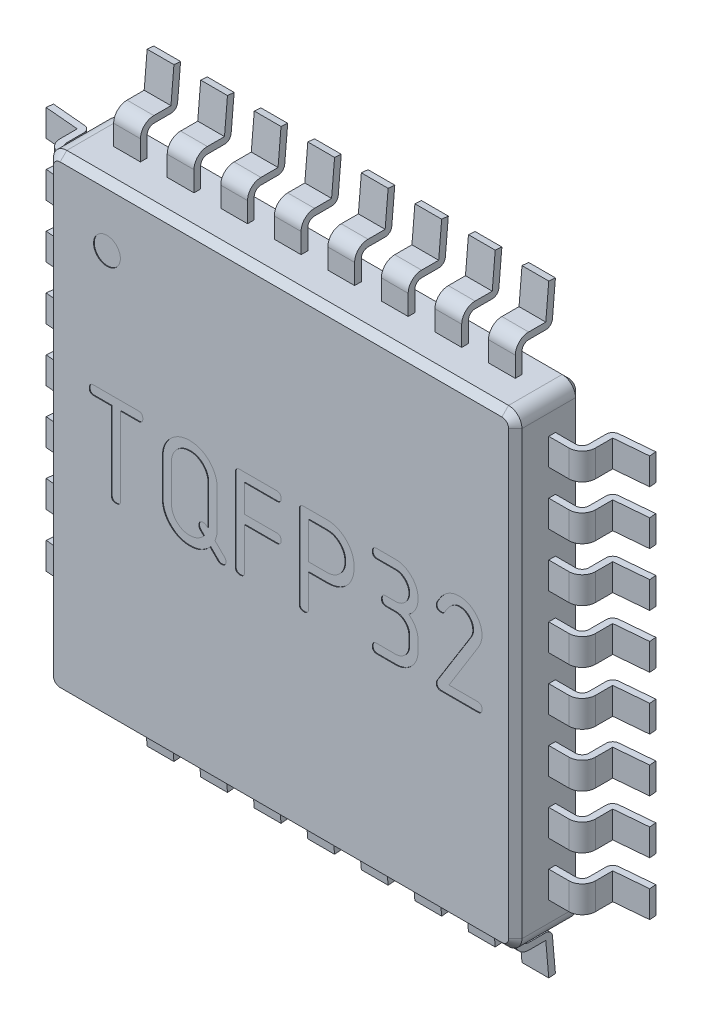
SolidWorks part; units mm, degrees
ref_plane "Спереди" through (0, 0, 0) normal (0, 0, 1) x (1, 0, 0)
ref_plane "Сверху" through (0, 0, 0) normal (0, 1, 0) x (1, 0, 0)
ref_plane "Справа" through (0, 0, 0) normal (1, 0, 0) x (0, 0, -1)
ref_axis "Ось1" through (0, 0, -0.055) along (0, 0, 1)
sketch "Эскиз1" plane through (0, 0, 0) normal (0, 0, 1) x (1, 0, 0)
  line L0 (0, 0) -> (-4.5, 0) construction
  line L1 (-3.5, -3.5) -> (3.5, -3.5)
  line L2 (-3.5, -3.5) -> (-3.5, 3.5)
  line L3 (-3.5, 3.5) -> (3.5, 3.5)
  line L4 (3.5, -3.5) -> (3.5, 3.5)
  line L5 (-3.5, -3.5) -> (3.5, 3.5) construction
  line L6 (-3.5, 3.5) -> (3.5, -3.5) construction
  line L7 (-4.5, -4.5) -> (4.5, -4.5)
  line L8 (-4.5, -4.5) -> (-4.5, 4.5)
  line L9 (-4.5, 4.5) -> (4.5, 4.5)
  line L10 (4.5, -4.5) -> (4.5, 4.5)
  line L11 (-4.5, -4.5) -> (4.5, 4.5) construction
  line L12 (-4.5, 4.5) -> (4.5, -4.5) construction
  point P0 (0, 0)
  point P6 (0, 0)
  point P13 (-3.5, 0.4)
  point P14 (-3.5, 1.2)
  point P15 (-3.5, 2)
  point P16 (-3.5, 2.8)
  point P17 (-3.5, -2.8)
  point P18 (-3.5, -2)
  point P19 (-3.5, -1.2)
  point P20 (-3.5, -0.4)
  dimension "D1" = 7
  dimension "D2" = 7
  dimension "D3" = 9
  dimension "D4" = 9
  dimension "D5" = 0.8
  dimension "D6" = 0.8
  dimension "D7" = 0.8
  dimension "D8" = 0.8
ref_plane "Плоскость1" through (0, 0, 0.1) normal (0, 0, 1) x (1, 0, 0)
ref_plane "Плоскость2" through (0, 2.8, 0) normal (0, 1, 0) x (-1, 0, 0)
sketch "Эскиз2" plane through (0, 0, 0.1) normal (0, 0, 1) x (1, 0, 0)
  line L0 (-3.5, 3.5) -> (3.5, 3.5) construction
  line L1 (-3.5, -3.5) -> (-3.5, 3.5) construction
  line L2 (-3.5, -3.5) -> (3.5, -3.5) construction
  line L3 (3.5, -3.5) -> (3.5, 3.5) construction
  line L4 (-3.3, 3.5) -> (3.3, 3.5)
  line L5 (-3.5, -3.3) -> (-3.5, 3.3)
  line L6 (-3.3, -3.5) -> (3.3, -3.5)
  line L7 (3.5, -3.3) -> (3.5, 3.3)
  arc A0 (-3.5, -3.3) -> (-3.3, -3.5) centre (-3.3, -3.3) ccw
  arc A1 (3.3, -3.5) -> (3.5, -3.3) centre (3.3, -3.3) ccw
  arc A2 (3.3, 3.5) -> (3.5, 3.3) centre (3.3, 3.3) cw
  arc A3 (-3.3, 3.5) -> (-3.5, 3.3) centre (-3.3, 3.3) ccw
  dimension "D1" = 0.2
extrude "Бобышка-Вытянуть1" add sketch "Эскиз2" along normal blind 1
chamfer "Фаска1" distance 0.1 angle 45 16 edges at (0, 3.5, 0.1) (-3.4414, 3.4414, 0.1) (3.4414, 3.4414, 0.1) (-3.5, 0, 0.1) (3.5, 0, 0.1) (-3.4414, -3.4414, 0.1) (3.4414, -3.4414, 0.1) (0, -3.5, 0.1) (0, 3.5, 1.1) (-3.4414, 3.4414, 1.1) (3.4414, 3.4414, 1.1) (-3.5, 0, 1.1) (3.5, 0, 1.1) (-3.4414, -3.4414, 1.1) (3.4414, -3.4414, 1.1) (0, -3.5, 1.1)
sketch "Эскиз3" plane through (0, 2.8, 0) normal (0, 1, 0) x (-1, 0, 0)
  line L0 (3.5, 0.5) -> (3.8, 0.5)
  line L1 (3.9, 0.4) -> (3.9, 0.1441)
  line L2 (3.9913, 0.0445) -> (4.5, 0)
  line L3 (4.95, 0) -> (-4.95, 0) construction
  line L4 (3.5, 0.6) -> (3.8, 0.6)
  line L5 (4, 0.4) -> (4, 0.1441)
  line L6 (4, 0.1441) -> (4.5087, 0.0996)
  line L7 (3.5, 0.5) -> (3.5, 0.6)
  line L8 (4.5, 0) -> (4.5087, 0.0996)
  arc A0 (3.9, 0.1441) -> (3.9913, 0.0445) centre (4, 0.1441) ccw
  arc A1 (3.8, 0.5) -> (3.9, 0.4) centre (3.8, 0.4) cw
  arc A2 (3.8, 0.6) -> (4, 0.4) centre (3.8, 0.4) cw
  arc A3 (4, 0.1441) -> (4, 0.1441) centre (4, 0.1441) ccw
  dimension "D1" = 0.1
  dimension "D2" = 0.6
  dimension "D3" = 5
  dimension "D4" = 0.5
  dimension "D5" = 0.1
extrude "Бобышка-Вытянуть2" add sketch "Эскиз3" along normal blind 0.2 and the other way blind 0.2
pattern_linear "Линейный массив1" count 8 spacing 0.8 along (0, -1, 0) of "Бобышка-Вытянуть2"
pattern_circular "Круговой массив1" count 4 over 360 about axis through (0, 0, -0.055) along (0, 0, 1) of "Бобышка-Вытянуть2", "Линейный массив1"
sketch "Эскиз4" plane through (0, 0, 1.1) normal (0, 0, 1) x (1, 0, 0)
  circle A0 centre (-2.6, 2.6) radius 0.2
  text T0 "TQFP32" font "ГОСТ тип А" height in points 6
  dimension "D1" = 0.4
  dimension "D2" = 3
  dimension "D3" = 0.6
extrude "Вырез-Вытянуть1" cut sketch "Эскиз4" against normal blind 0.01
